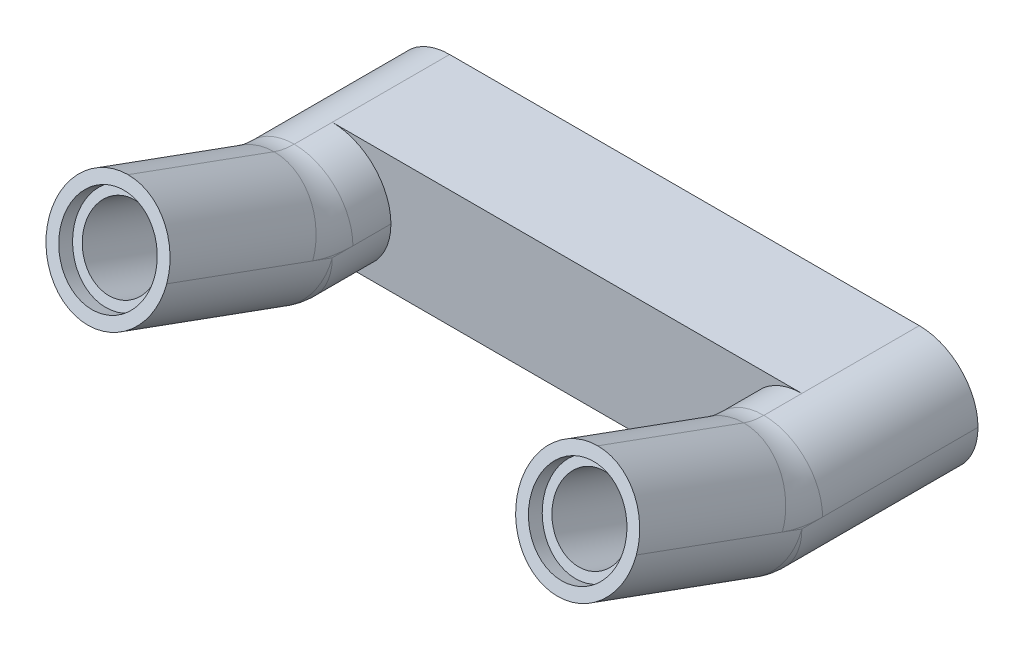
SolidWorks part; units mm, degrees
ref_plane "Front Plane" through (0, 0, 0) normal (1, 0, 0) x (0, 1, 0)
ref_plane "Top Plane" through (0, 0, 0) normal (0, 0, 1) x (0, 1, 0)
ref_plane "Right Plane" through (0, 0, 0) normal (0, 1, 0) x (-1, 0, 0)
sketch "Sketch1" plane through (0, 0, 0) normal (1, 0, 0) x (0, 1, 0)
  line L0 (2.9776, 20.8861) -> (0.2412, 13.3681)
  line L1 (0, 0) -> (8, 0)
  line L2 (0, 0) -> (0, 12)
  line L4 (8, 0) -> (8, 11.2947)
  line L7 (2.9776, 20.8861) -> (4.3455, 24.6444)
  line L8 (4.3455, 24.6444) -> (11.863, 21.9082)
  line L9 (11.863, 21.9082) -> (10.4974, 18.1561)
  line L10 (10.4974, 18.1561) -> (8, 11.2947)
  arc A0 (0.2412, 13.3681) -> (0, 12) centre (4, 12) ccw
  dimension "D3" = 12
  dimension "D5" = 8
  dimension "D6" = 160
extrude "Boss-Extrude1" add sketch "Sketch1" along normal blind 40
fillet "Fillet1" radius 4 1 edges at (20, 8, 11.2947)
sketch "Sketch2" plane through (0, 0, 0) normal (0, 0, -1) x (1, 0, 0)
  line L0 (40, 0) -> (0, 0) construction
  line L1 (0, 0) -> (0, -8) construction
  line L2 (40, 0) -> (40, -8) construction
  circle A0 centre (4, -4) radius 2.55
  circle A1 centre (36, -4) radius 2.55
  dimension "D1" = 5.1
  dimension "D2" = 4
  dimension "D3" = 4
  dimension "D4" = 4
  dimension "D5" = 4
extrude "Cut-Extrude1" cut sketch "Sketch2" against normal blind 8.1
sketch "Sketch3" plane through (0, 0, 8.1) normal (0, 0, -1) x (1, 0, 0)
  circle A0 centre (4, -4) radius 3.175
  circle A1 centre (36, -4) radius 3.175
  dimension "D1" = 6.35
extrude "Cut-Extrude2" cut sketch "Sketch3" along normal blind 1.1
sketch "Sketch4" plane through (0, 0, 0) normal (0, 0, -1) x (1, 0, 0)
  circle A1 centre (36, -4) radius 3.175
  circle A2 centre (36, -4) radius 3.175
  circle A3 centre (4, -4) radius 3.175
  circle A4 centre (4, -4) radius 3.175
  dimension "D1" = 0
  dimension "D2" = 0
extrude "Cut-Extrude3" cut sketch "Sketch4" against normal blind 1.1
fillet "Fillet2" radius 4 12 edges at (0, 2.2934, 19.0062) (0, 0, 6) (0, 10.0521, 16.9328) (0, 8, 5.2947) (40, 0, 6) (40, 0.0608, 12.6946) (40, 10.0521, 16.9328) (40, 8.0608, 11.284) (0, 0.0608, 12.6946) (0, 8.0608, 11.284) (40, 2.2934, 19.0062) (40, 8, 5.2947)
sketch "Sketch5" plane through (0, 8.4289, 23.1582) normal (0, 0.342, 0.9397) x (-1, 0, 0)
  circle A0 centre (-36, 0.3455) radius 2.55
  circle A1 centre (-4, 0.3455) radius 2.55
  dimension "D1" = 5.1
extrude "Cut-Extrude4" cut sketch "Sketch5" against normal blind 8.1
sketch "Sketch6" plane through (0, 8.4289, 23.1582) normal (0, 0.342, 0.9397) x (-1, 0, 0)
  circle A0 centre (-36, 0.3455) radius 3.175
  circle A1 centre (-4, 0.3455) radius 3.175
  dimension "D1" = 6.35
extrude "Cut-Extrude5" cut sketch "Sketch6" against normal blind 1
sketch "Sketch7" plane through (0, 5.6585, 15.5466) normal (0, 0.342, 0.9397) x (-1, 0, 0)
  circle A1 centre (-4, 0.3455) radius 3.175
  circle A2 centre (-4, 0.3455) radius 3.175
  circle A3 centre (-36, 0.3455) radius 3.175
  circle A4 centre (-36, 0.3455) radius 3.175
  dimension "D1" = 0
  dimension "D2" = 0
extrude "Cut-Extrude6" cut sketch "Sketch7" along normal blind 1.1
sketch "Sketch8" plane through (0, 0, 0) normal (0, -1, 0) x (1, 0, 0)
  line L0 (36, 24.6444) -> (4, 24.6444) construction
  line L1 (8, 24.6444) -> (32, 24.6444)
  line L2 (8, 24.6444) -> (8, 8)
  line L3 (8, 8) -> (32, 8)
  line L4 (32, 24.6444) -> (32, 8)
  line L5 (36, 0) -> (4, 0) construction
  line L6 (40, 12) -> (40, 10.5894) construction
  line L7 (0, 10.5894) -> (0, 12) construction
  dimension "D1" = 8
  dimension "D2" = 8
  dimension "D3" = 8
extrude "Cut-Extrude7" cut sketch "Sketch8" against normal through all
fillet "Fillet3" radius 4 12 edges at (8, 8.0608, 11.284) (8, 0, 10) (8, 0.0608, 12.6946) (32, 0, 10) (32, 0.0608, 12.6946) (32, 8.0608, 11.284) (8, 10.0521, 16.9328) (8, 2.2934, 19.0062) (32, 2.2934, 19.0062) (32, 10.0521, 16.9328) (8, 8, 9.2947) (32, 8, 9.2947)
sketch "Sketch9" plane through (0, 0, 0) normal (0, -1, 0) x (1, 0, 0)
  line L0 (4, 1.25) -> (36, 1.25) construction
  line L1 (4, 8) -> (4, 0) construction
  line L2 (36, 0) -> (36, 8) construction
  line L3 (36, 0) -> (4, 0) construction
  text T0 "<b>FAST5</b>" font "Century Gothic" height 5
  dimension "D1" = 1.25
extrude "Cut-Extrude8" cut sketch "Sketch9" against normal blind 1
